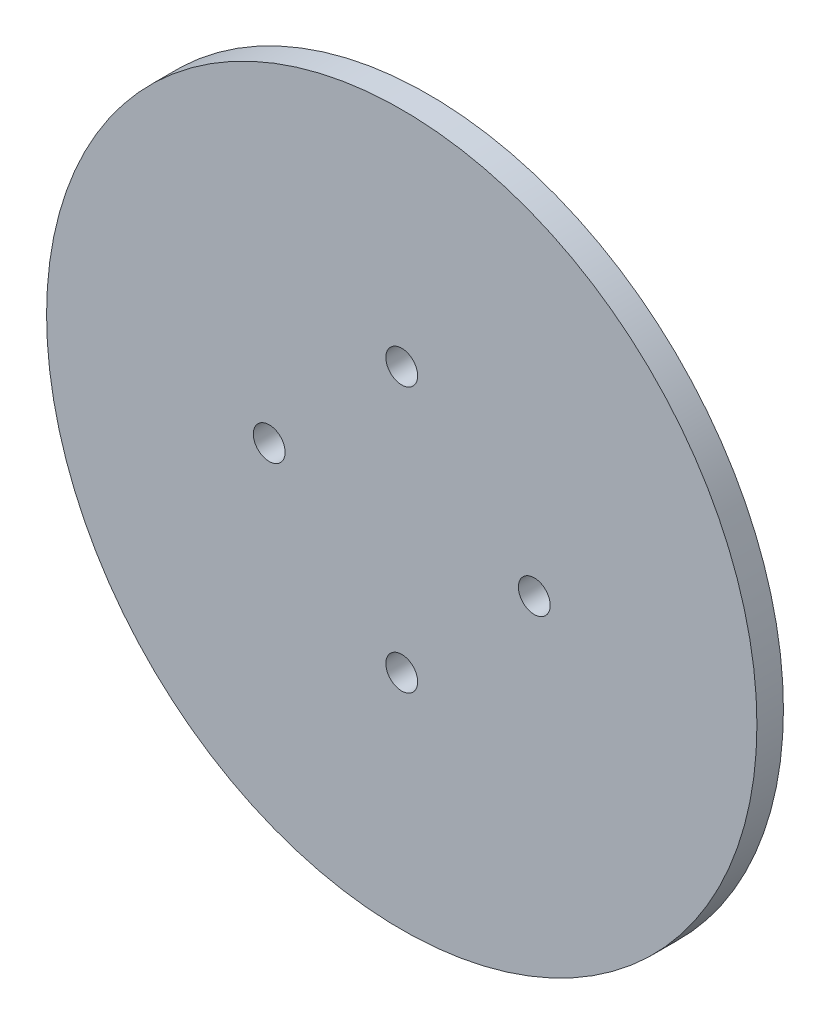
SolidWorks part; units mm, degrees
ref_plane "Płaszczyzna przednia" through (0, 0, 0) normal (0, 0, 1) x (1, 0, 0)
ref_plane "Płaszczyzna górna" through (0, 0, 0) normal (0, 1, 0) x (1, 0, 0)
ref_plane "Płaszczyzna prawa" through (0, 0, 0) normal (1, 0, 0) x (0, 0, -1)
sketch "Szkic1" plane through (0, 0, 0) normal (0, 0, 1) x (1, 0, 0)
  line L0 (0, 0) -> (0, 67) construction
  circle A0 centre (0, 0) radius 67
  circle A1 centre (0, 0) radius 25 construction
  circle A2 centre (0, 25) radius 3
  circle A3 centre (25, 0) radius 3
  circle A4 centre (0, -25) radius 3
  circle A5 centre (-25, 0) radius 3
  point P16 (0, 0)
  dimension "D1" = 134
  dimension "D2" = 6
  dimension "D3" = 50
extrude "Dodanie-wyciągnięcie1" add sketch "Szkic1" along normal blind 5
sketch "Szkic2" plane through (0, 0, 5) normal (0, 0, 1) x (1, 0, 0)
  line L0 (-111.2275, 42.2933) -> (-67.2275, 42.2933) construction
  line L1 (6.0156, 12.8251) -> (-16.9878, 12.8251)
  line L2 (-6.5902, 8.1949) -> (6.3471, 8.1949)
  line L3 (-25, 0) -> (25, 0) construction
  line L4 (0, 25) -> (0, -25) construction
  line L5 (-6.742, 2.8333) -> (6.751, 2.8333)
  line L6 (-6.742, -2.3415) -> (6.751, -2.3415)
  line L7 (-6.0156, -12.8251) -> (16.9878, -12.8251)
  line L8 (6.5902, -8.1949) -> (-6.3471, -8.1949)
  circle A0 centre (-16.2453, 8.1949) radius 1.9374
  circle A2 centre (16.2453, -8.1949) radius 1.9374
  spline S0 degree 3 poles (6.0156, 12.8251) (10.5109, 13.3599) (16.4953, 4.6727) (10.4162, -2.613) (6.751, -2.3415) knots 0 0 0 0 0.552477 1 1 1 1
  spline S1 degree 3 poles (6.751, 2.8333) (8.3665, 3.075) (9.0704, 5.5978) (7.625, 7.9998) (6.3471, 8.1949) knots 0 0 0 0 0.494793 1 1 1 1
  spline S2 degree 3 poles (-16.9878, 12.8251) (-21.3984, 13.1574) (-22.5461, 2.5584) (-11.8282, 3.5339) (-9.7967, 8.1861) (-6.5902, 8.1949) knots 0 0 0 0 0.432021 0.673133 1 1 1 1
  spline S6 degree 3 poles (-6.0156, -12.8251) (-10.5458, -13.3417) (-16.4148, -4.6317) (-10.492, 2.9663) (-6.742, 2.8333) knots 0 0 0 0 0.544343 1 1 1 1
  spline S7 degree 3 poles (-6.742, -2.3415) (-8.3839, -2.6395) (-9.1066, -5.4858) (-7.6357, -7.9911) (-6.3471, -8.1949) knots 0 0 0 0 0.52646 1 1 1 1
  spline S8 degree 3 poles (16.9878, -12.8251) (21.3984, -13.1574) (22.5461, -2.5584) (11.8282, -3.5339) (9.7967, -8.1861) (6.5902, -8.1949) knots 0 0 0 0 0.432021 0.673133 1 1 1 1
  point P22 (0, 0)
